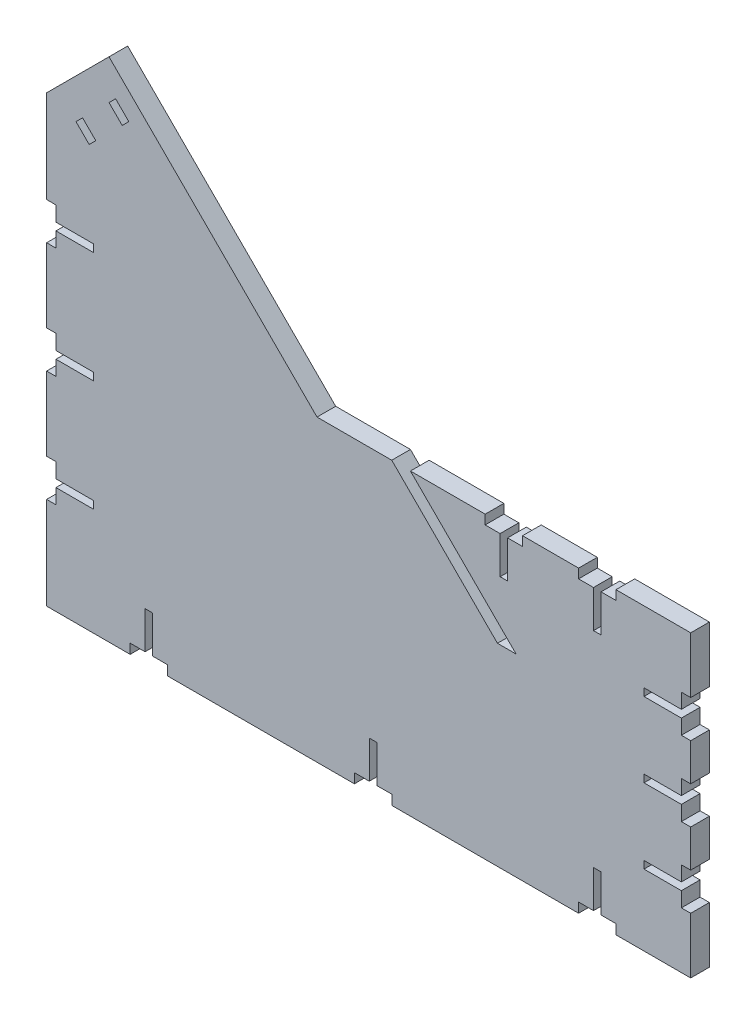
SolidWorks part; units mm, degrees
ref_plane "Front Plane" through (0, 0, 0) normal (0, 0, 1) x (1, 0, 0)
ref_plane "Top Plane" through (0, 0, 0) normal (0, 1, 0) x (1, 0, 0)
ref_plane "Right Plane" through (0, 0, 0) normal (1, 0, 0) x (0, 0, -1)
sketch "Sketch1" plane through (0, 0, 0) normal (0, 0, 1) x (1, 0, 0)
  line L0 (0, 0) -> (127, 0)
  line L1 (127, 0) -> (127, 101.6)
  line L3 (0, 101.6) -> (0, 0) construction
  line L4 (0, 101.6) -> (-70.6924, 172.2924)
  line L5 (-70.6924, 172.2924) -> (-91.8969, 151.088)
  line L6 (-91.8969, 151.088) -> (-91.8969, 0)
  line L7 (-91.8969, 0) -> (0, 0)
  line L8 (127, 101.6) -> (0, 101.6)
  dimension "D1" = 127
  dimension "D2" = 101.6
  dimension "D3" = 135
  dimension "D4" = 29.9876
  dimension "D5" = 151.088
extrude "Boss-Extrude1" add sketch "Sketch1" along normal blind 6.35
sketch "Sketch2" plane through (0, 0, 0) normal (0, 0, -1) x (-1, 0, 0)
  line L0 (0, 101.6) -> (-25.4, 101.6) construction
  line L1 (-127, 101.6) -> (0, 101.6) construction
  line L2 (-25.4, 101.6) -> (-31.75, 101.6)
  line L3 (-25.4, 101.6) -> (-61.321, 65.679)
  line L4 (-31.75, 101.6) -> (-67.671, 65.679)
  line L5 (-67.671, 65.679) -> (-61.321, 65.679)
  line L6 (-49.7105, 83.6395) -> (-43.3605, 83.6395) construction
  line L7 (-31.75, 101.6) -> (-49.7105, 83.6395)
  point P12 (-64.496, 65.679)
  line M12 (0, 101.6) -> (-127, 101.6)
  dimension "D1" = 25.4
  dimension "D2" = 6.35
  dimension "D3" = 50.8
  dimension "D4" = 45
  dimension "D5" = 45
  dimension "D6" = 50.8
  dimension "D7" = 135
  dimension "D8" = 25.4
sketch "Sketch3" plane through (0, 0, 0) normal (0, 0, -1) x (-1, 0, 0)
  line L0 (70.6924, 172.2924) -> (61.7122, 163.3122) construction
  line L1 (0, 101.6) -> (70.6924, 172.2924) construction
  line L2 (59.4671, 161.0671) -> (63.9572, 165.5572)
  line L3 (59.4671, 161.0671) -> (63.9572, 156.577) construction
  line L5 (68.4474, 161.0671) -> (63.9572, 165.5572) construction
  line L6 (70.6924, 172.2924) -> (91.8969, 151.088) construction
  line L7 (63.9572, 156.577) -> (68.4474, 161.0671)
  line L8 (63.9572, 156.577) -> (66.2023, 154.3319)
  line L9 (68.4474, 161.0671) -> (70.6924, 158.822)
  line L10 (70.6924, 158.822) -> (66.2023, 154.3319)
  line L11 (-127, 25.4) -> (-127, 0)
  line L12 (-127, 50.8) -> (-127, 101.6) construction
  line L13 (-127, 0) -> (-127, 50.8) construction
  line L14 (-25.4, 0) -> (-12.7, 0)
  line L15 (-127, 82.55) -> (-127, 69.85)
  line L16 (0, 101.6) -> (-63.5, 101.6) construction
  line L17 (-127, 44.45) -> (-127, 57.15)
  line L18 (-127, 19.05) -> (-127, 31.75)
  line L19 (-63.5, 101.6) -> (-127, 101.6) construction
  line L20 (-101.6, 101.6) -> (-88.9, 101.6)
  line L21 (-69.85, 101.6) -> (-57.15, 101.6)
  line L22 (70.6924, 172.2924) -> (0, 101.6) construction
  line L23 (30.8561, 132.4561) -> (39.8363, 141.4363)
  line L24 (91.8969, 119.666) -> (91.8969, 106.966)
  line L25 (91.8969, 0) -> (91.8969, 75.544) construction
  line L26 (91.8969, 75.544) -> (91.8969, 151.088) construction
  line L27 (91.8969, 81.894) -> (91.8969, 69.194)
  line L28 (91.8969, 44.122) -> (91.8969, 31.422)
  line L29 (30.8561, 132.4561) -> (33.1011, 130.211)
  line L30 (-127, 82.55) -> (-123.825, 82.55)
  line L31 (-127, 82.55) -> (-127, 69.85)
  line L32 (-127, 69.85) -> (-123.825, 69.85)
  line L33 (-123.825, 82.55) -> (-123.825, 69.85) construction
  line L34 (-127, 57.15) -> (-123.825, 57.15)
  line L35 (-127, 57.15) -> (-127, 44.45)
  line L36 (-127, 44.45) -> (-123.825, 44.45)
  line L37 (-123.825, 57.15) -> (-123.825, 44.45) construction
  line L38 (-127, 31.75) -> (-123.825, 31.75)
  line L39 (-127, 31.75) -> (-127, 19.05)
  line L40 (-127, 19.05) -> (-123.825, 19.05)
  line L41 (-123.825, 31.75) -> (-123.825, 19.05) construction
  line L42 (-101.6, 101.6) -> (-88.9, 101.6)
  line L43 (-101.6, 101.6) -> (-101.6, 98.425)
  line L44 (-101.6, 98.425) -> (-88.9, 98.425) construction
  line L45 (-88.9, 101.6) -> (-88.9, 98.425)
  line L46 (-69.85, 101.6) -> (-57.15, 101.6)
  line L47 (-69.85, 101.6) -> (-69.85, 98.425)
  line L48 (-69.85, 98.425) -> (-57.15, 98.425) construction
  line L49 (-57.15, 101.6) -> (-57.15, 98.425)
  line L54 (39.8363, 141.4363) -> (42.0814, 139.1913)
  line L55 (42.0814, 139.1913) -> (33.1011, 130.211)
  line L56 (-123.825, 77.4827) -> (-123.825, 74.9173) construction
  line L57 (91.8969, 119.666) -> (88.7219, 119.666)
  line L58 (91.8969, 119.666) -> (91.8969, 106.966)
  line L59 (91.8969, 106.966) -> (88.7219, 106.966)
  line L60 (88.7219, 119.666) -> (88.7219, 106.966) construction
  line L61 (91.8969, 81.894) -> (88.7219, 81.894)
  line L62 (91.8969, 81.894) -> (91.8969, 69.194)
  line L63 (91.8969, 69.194) -> (88.7219, 69.194)
  line L64 (88.7219, 81.894) -> (88.7219, 69.194) construction
  line L65 (91.8969, 44.122) -> (88.7219, 44.122)
  line L66 (91.8969, 44.122) -> (91.8969, 31.422)
  line L67 (91.8969, 31.422) -> (88.7219, 31.422)
  line L68 (88.7219, 44.122) -> (88.7219, 31.422) construction
  line L69 (-101.6, 0) -> (-101.6, 3.302)
  line L70 (-123.825, 77.4827) -> (-111.125, 77.4827)
  line L71 (-123.825, 77.4827) -> (-123.825, 74.9173) construction
  line L72 (-123.825, 74.9173) -> (-111.125, 74.9173)
  line L73 (-111.125, 77.4827) -> (-111.125, 74.9173)
  line L74 (91.8969, 0) -> (-127, 0) construction
  line L75 (-101.6, 3.302) -> (-88.9, 3.302) construction
  line L76 (-88.9, 3.302) -> (-88.9, 0)
  line L77 (-101.6, 0) -> (-88.9, 0)
  line L78 (-25.4, 0) -> (-25.4, 3.302)
  line L79 (-25.4, 3.302) -> (-12.7, 3.302) construction
  line L80 (-12.7, 3.302) -> (-12.7, 0)
  line L81 (50.8, 0) -> (50.8, 3.302)
  line L82 (50.8, 3.302) -> (63.5, 3.302) construction
  line L83 (63.5, 3.302) -> (63.5, 0)
  line L84 (63.5, 0) -> (50.8, 0)
  line L85 (-93.9673, 3.302) -> (-96.5327, 3.302) construction
  line L86 (-96.5327, 3.302) -> (-96.5327, 16.002)
  line L87 (-96.5327, 16.002) -> (-93.9673, 16.002)
  line L88 (-93.9673, 16.002) -> (-93.9673, 3.302)
  line L89 (-17.7673, 3.302) -> (-20.3327, 3.302) construction
  line L90 (-20.3327, 3.302) -> (-20.3327, 16.002)
  line L91 (-20.3327, 16.002) -> (-17.7673, 16.002)
  line L92 (-17.7673, 16.002) -> (-17.7673, 3.302)
  line L93 (58.4327, 3.302) -> (55.8673, 3.302) construction
  line L94 (55.8673, 3.302) -> (55.8673, 16.002)
  line L95 (55.8673, 16.002) -> (58.4327, 16.002)
  line L96 (58.4327, 16.002) -> (58.4327, 3.302)
  line L97 (-123.825, 24.1173) -> (-123.825, 26.6827) construction
  line L98 (-123.825, 26.6827) -> (-111.125, 26.6827)
  line L99 (-111.125, 26.6827) -> (-111.125, 24.1173)
  line L100 (-111.125, 24.1173) -> (-123.825, 24.1173)
  line L101 (-123.825, 49.5173) -> (-123.825, 52.0827) construction
  line L102 (-123.825, 52.0827) -> (-111.125, 52.0827)
  line L103 (-111.125, 52.0827) -> (-111.125, 49.5173)
  line L104 (-111.125, 49.5173) -> (-123.825, 49.5173)
  line L105 (-93.9673, 98.425) -> (-96.5327, 98.425) construction
  line L106 (-96.5327, 98.425) -> (-96.5327, 85.725)
  line L107 (-96.5327, 85.725) -> (-93.9673, 85.725)
  line L108 (-93.9673, 85.725) -> (-93.9673, 98.425)
  line L109 (-62.23, 98.425) -> (-64.77, 98.425) construction
  line L110 (-64.77, 98.425) -> (-64.77, 85.725)
  line L111 (-64.77, 85.725) -> (-62.23, 85.725)
  line L112 (-62.23, 85.725) -> (-62.23, 98.425)
  line L113 (88.7219, 112.0333) -> (88.7219, 114.5987) construction
  line L114 (88.7219, 114.5987) -> (76.0219, 114.5987)
  line L115 (76.0219, 114.5987) -> (76.0219, 112.0333)
  line L116 (76.0219, 112.0333) -> (88.7219, 112.0333)
  line L117 (88.7219, 74.2613) -> (88.7219, 76.8267) construction
  line L118 (88.7219, 76.8267) -> (76.0219, 76.8267)
  line L119 (76.0219, 76.8267) -> (76.0219, 74.2613)
  line L120 (76.0219, 74.2613) -> (88.7219, 74.2613)
  line L121 (88.7219, 36.4893) -> (88.7219, 39.0547) construction
  line L122 (88.7219, 39.0547) -> (76.0219, 39.0547)
  line L123 (76.0219, 39.0547) -> (76.0219, 36.4893)
  line L124 (76.0219, 36.4893) -> (88.7219, 36.4893)
  line L125 (-123.825, 44.45) -> (-123.825, 49.5173)
  line L126 (-123.825, 52.0827) -> (-123.825, 57.15) construction
  line L127 (-123.825, 82.55) -> (-123.825, 77.4827)
  line L128 (-123.825, 74.9173) -> (-123.825, 69.85)
  line L129 (-123.825, 57.15) -> (-123.825, 52.0827)
  line L130 (-123.825, 52.0827) -> (-123.825, 57.15)
  line L131 (-123.825, 26.6827) -> (-123.825, 31.75)
  line L132 (-123.825, 19.05) -> (-123.825, 24.1173)
  line L133 (-101.6, 3.302) -> (-96.5327, 3.302)
  line L135 (-101.6, 98.425) -> (-96.5327, 98.425)
  line L136 (-93.9673, 98.425) -> (-88.9, 98.425)
  line L137 (-64.77, 98.425) -> (-69.85, 98.425)
  line L138 (-62.23, 98.425) -> (-57.15, 98.425)
  line L139 (-93.9673, 3.302) -> (-88.9, 3.302)
  line L140 (-25.4, 3.302) -> (-20.3327, 3.302)
  line L141 (-17.7673, 3.302) -> (-12.7, 3.302)
  line L142 (50.8, 3.302) -> (55.8673, 3.302)
  line L143 (58.4327, 3.302) -> (63.5, 3.302)
  line L144 (88.7219, 39.0547) -> (88.7219, 44.122)
  line L145 (88.7219, 31.422) -> (88.7219, 36.4893)
  line L146 (88.7219, 69.194) -> (88.7219, 74.2613)
  line L147 (88.7219, 76.8267) -> (88.7219, 81.894)
  line L148 (88.7219, 106.966) -> (88.7219, 112.0333)
  line L149 (88.7219, 114.5987) -> (88.7219, 119.666)
  point P8 (61.7122, 163.3122)
  point P27 (-127, 76.2)
  point P30 (-127, 50.8)
  point P33 (-127, 25.4)
  point P34 (-95.25, 101.6)
  point P36 (-95.25, 101.6)
  point P39 (-63.5, 85.725)
  point P41 (-31.75, 101.6)
  point P42 (-63.5, 101.6)
  point P45 (35.3462, 136.9462)
  point P53 (91.8969, 113.316)
  point P56 (91.8969, 75.544)
  point P59 (91.8969, 37.772)
  point P70 (-95.25, 3.302)
  point P82 (-123.825, 76.2)
  point P102 (-19.05, 3.302)
  point P107 (57.15, 3.302)
  point P112 (-123.825, 25.4)
  point P117 (-123.825, 50.8)
  point P122 (-95.25, 98.425)
  point P127 (-63.5, 98.425)
  point P132 (88.7219, 113.316)
  point P137 (88.7219, 75.544)
  point P142 (88.7219, 37.772)
  point P145 (0, 0)
  point P146 (0, 0)
  line M40 (-127, 0) -> (91.8969, 0)
  line M41 (91.8969, 0) -> (91.8969, 151.088)
  line M44 (0, 101.6) -> (-127, 101.6)
  line M45 (-127, 101.6) -> (-127, 0)
  dimension "D1" = 12.7
  dimension "D2" = 9.525
  dimension "D3" = 6.35
  dimension "D4" = 6.35
  dimension "D5" = 6.35
  dimension "D6" = 3.175
  dimension "D7" = 3.175
  dimension "D8" = 12.7
  dimension "D9" = 12.7
  dimension "D10" = 12.7
  dimension "D11" = 25.4
  dimension "D12" = 12.7
  dimension "D13" = 12.7
  dimension "D14" = 12.7
  dimension "D15" = 31.75
  dimension "D16" = 12.7
  dimension "D17" = 75.544
  dimension "D18" = 12.7
  dimension "D19" = 12.7
  dimension "D20" = 12.7
  dimension "D21" = 3.175
  dimension "D22" = 3.175
  dimension "D23" = 3.175
  dimension "D24" = 3.175
  dimension "D25" = 3.175
  dimension "D26" = 3.302
  dimension "D27" = 3.175
  dimension "D28" = 3.175
  dimension "D29" = 12.7
  dimension "D30" = 3.175
  dimension "D31" = 3.175
  dimension "D32" = 3.175
  dimension "D33" = 2.5654
  dimension "D34" = 12.7
  dimension "D35" = 25.4
  dimension "D36" = 63.5
  dimension "D37" = 63.5
  dimension "D38" = 3.302
  dimension "D39" = 12.7
  dimension "D40" = 12.7
  dimension "D41" = 3.302
  dimension "D42" = 2.5654
  dimension "D43" = 12.7
  dimension "D44" = 12.7
  dimension "D45" = 2.5654
  dimension "D46" = 12.7
  dimension "D47" = 2.5654
  dimension "D48" = 12.7
  dimension "D49" = 2.5654
  dimension "D50" = 12.7
  dimension "D51" = 1.27
  dimension "D52" = 12.7
  dimension "D53" = 2.5654
  dimension "D54" = 2.5654
  dimension "D55" = 12.7
  dimension "D56" = 2.5654
  dimension "D57" = 12.7
  dimension "D58" = 12.7
  dimension "D59" = 2.5654
  dimension "D60" = 12.7
  dimension "D61" = 2.5654
extrude "Cut-Extrude2" cut sketch "Sketch2" against normal blind 127 and the other way blind 2.54 contours L4 L5 L3 M12 region at (46.5355, 83.6395, 0)
extrude "Cut-Extrude4" cut sketch "Sketch3" against normal blind 127 and the other way blind 127 contours L108 L136 L45 L43 L135 L106 L107 M44 | L112 L138 L49 L47 L137 L110 L111 M44 | L128 L72 L73 L70 L127 L30 L32 M45 | L129 L34 L36 L125 L104 L103 L102 M45 | L40 L132 L100 L99 L98 L131 L38 M45 | L139 L88 L87 L86 L133 L69 L76 M40 | L141 L92 L91 L90 L140 L78 L80 M40 | L143 L96 L95 L94 L142 L81 L83 M40 | L145 L67 L65 L144 L122 L123 L124 M41 | L147 L118 L119 L120 L146 L63 L61 M41 | L149 L114 L115 L116 L148 L59 L57 M41 | L10 L9 L7 L8 region at (-67.3248, 157.6995, 0) region at (121.8652, 25.4, 0) region at (63.5, 96.4847, 0) region at (95.25, 96.4652, 0) region at (121.8652, 76.2, 0) region at (121.8652, 50.8, 0) region at (-86.7621, 113.316, 0) region at (-86.7621, 75.544, 0) region at (-86.7621, 37.772, 0) region at (-57.15, 5.1493, 0) region at (19.05, 5.1493, 0) region at (95.25, 5.1493, 0)
sketch "Sketch4" plane through (0, 0, 0) normal (0, 0, 1) x (1, 0, 0)
  line L0 (-81.9177, 147.5967) -> (-79.6727, 149.8418)
  line L1 (-81.9177, 147.5967) -> (-77.4276, 143.1066)
  line L2 (-77.4276, 143.1066) -> (-75.1826, 145.3517)
  line L3 (-75.1826, 145.3517) -> (-79.6727, 149.8418)
  line L5 (-70.6924, 158.822) -> (-66.2023, 154.3319) construction
  line L6 (-70.6924, 172.2924) -> (-91.8969, 151.088) construction
  dimension "D1" = 3.175
  dimension "D2" = 6.35
  dimension "D3" = 12.7
  dimension "D4" = 9.525
extrude "Cut-Extrude5" cut sketch "Sketch4" against normal blind 127 and the other way blind 127 contours L0 L3 L2 L1
